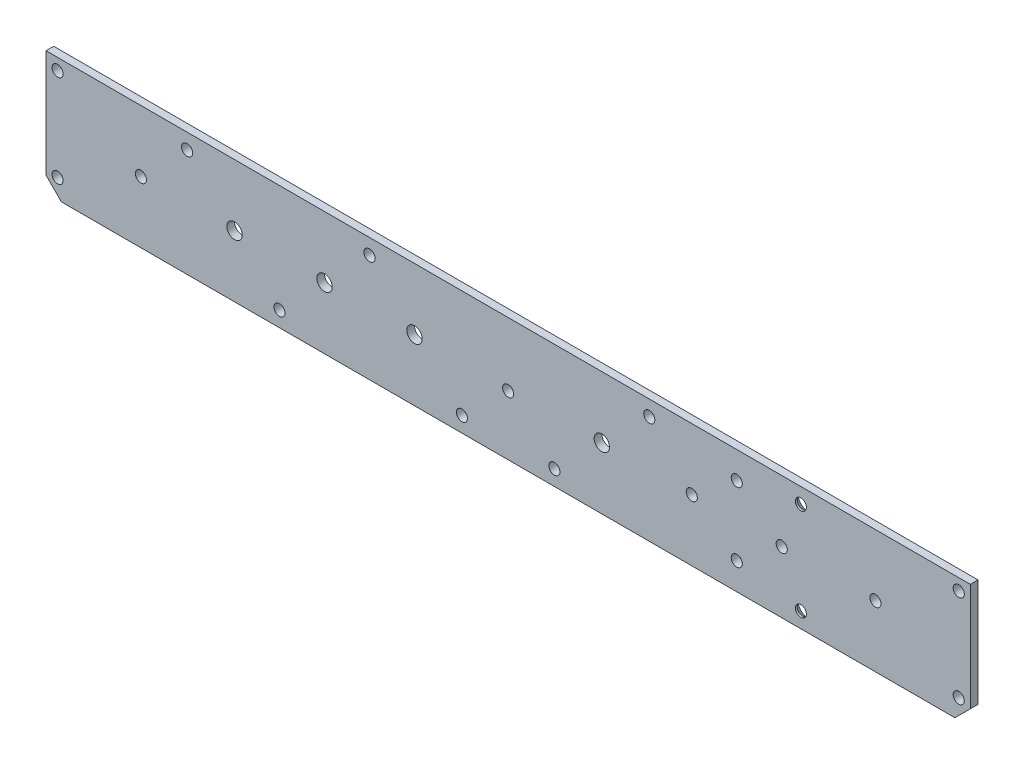
SolidWorks part; units mm, degrees
ref_plane "Front Plane" through (0, 0, 0) normal (0, 0, 1) x (1, 0, 0)
ref_plane "Top Plane" through (0, 0, 0) normal (0, 1, 0) x (1, 0, 0)
ref_plane "Right Plane" through (0, 0, 0) normal (1, 0, 0) x (0, 0, -1)
sketch "Sketch1" plane through (0, 0, 0) normal (0, 0, 1) x (1, 0, 0)
  line L1 (0, 0) -> (381, 0)
  line L2 (0, 0) -> (0, 50.8)
  line L3 (0, 50.8) -> (381, 50.8)
  line L4 (381, 0) -> (381, 50.8)
  dimension "D1" = 50.8
  dimension "D2" = 381
extrude "Boss-Extrude1" add sketch "Sketch1" along normal blind 3.175
sketch "Sketch2" plane through (0, 0, 3.175) normal (0, 0, 1) x (1, 0, 0)
  line L0 (77.724, 25.4) -> (114.808, 25.4) construction
  line L1 (190.5, 50.8) -> (190.5, 0) construction
  line L2 (381, 50.8) -> (0, 50.8) construction
  line L3 (0, 0) -> (381, 0) construction
  line L4 (266.192, 25.4) -> (303.276, 25.4) construction
  line L5 (0, 6.35) -> (0, 0)
  line L6 (0, 50.8) -> (0, 0) construction
  line L7 (0, 0) -> (6.35, 0)
  line L8 (6.35, 0) -> (0, 6.35)
  line L9 (381, 0) -> (374.65, 0)
  line L10 (374.65, 0) -> (381, 6.35)
  line L11 (381, 6.35) -> (381, 0)
  line L12 (381, 0) -> (381, 50.8) construction
  circle A0 centre (39.116, 25.4) radius 2.286
  circle A1 centre (190.5, 24.6062) radius 2.286
  circle A2 centre (114.808, 25.4) radius 3.175
  circle A3 centre (77.724, 25.4) radius 3.175
  circle A4 centre (151.892, 25.4) radius 3.175
  circle A5 centre (229.108, 25.4) radius 3.175
  circle A6 centre (303.276, 25.4) radius 2.286
  circle A7 centre (266.192, 25.4) radius 2.286
  circle A8 centre (341.884, 25.4) radius 2.286
  circle A9 centre (58.166, 44.45) radius 2.286
  circle A10 centre (171.45, 6.35) radius 2.286
  circle A11 centre (209.55, 6.35) radius 2.286
  circle A13 centre (133.35, 44.45) radius 2.286
  circle A14 centre (248.666, 44.45) radius 2.286
  circle A15 centre (96.266, 6.35) radius 2.286
  circle A19 centre (4.7625, 46.0375) radius 2.286
  circle A20 centre (4.7625, 7.9375) radius 2.286
  circle A21 centre (376.2375, 7.9375) radius 2.286
  circle A22 centre (376.2375, 46.0375) radius 2.286
  circle A24 centre (311.15, 44.45) radius 2.286
  circle A25 centre (284.734, 11.1125) radius 2.286
  circle A26 centre (284.734, 39.6875) radius 2.286
  circle A27 centre (311.15, 6.35) radius 2.286
  point P17 (190.5, 25.4)
  point P38 (96.266, 25.4)
  point P49 (284.734, 25.4)
  dimension "D2" = 4.572
  dimension "D5" = 6.35
  dimension "D7" = 4.572
  dimension "D12" = 4.572
  dimension "D15" = 4.572
  dimension "D16" = 4.572
  dimension "D19" = 4.572
  dimension "D21" = 6.35
  dimension "D27" = 4.572
  dimension "D29" = 11.1125
  dimension "D8" = 4.572
  dimension "D10" = 4.572
  dimension "D13" = 6.35
  dimension "D3" = 38.608
  dimension "D4" = 0.7937
  dimension "D6" = 14.2875
  dimension "D9" = 69.85
  dimension "D11" = 6.35
  dimension "D22" = 6.35
  dimension "D25" = 4.7625
  dimension "D26" = 4.7625
  dimension "D28" = 7.9375
extrude "Cut-Extrude1" cut sketch "Sketch2" against normal up to next (3.175 mm away)
chamfer "Chamfer1" distance 2.3813 angle 41 2 edges at (308.864, 44.45, 0) (308.864, 6.35, 0) first distance on face at (308.864, 44.45, 0) first distance on face at (308.864, 6.35, 0)
